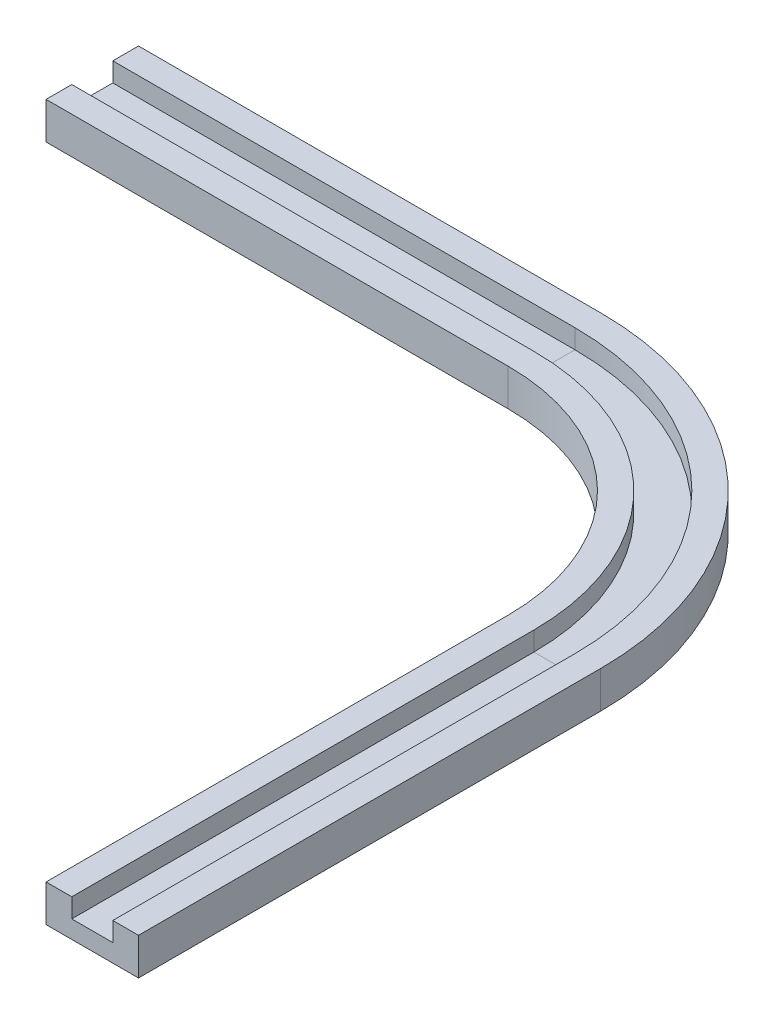
SolidWorks part; units mm, degrees
other "Published References"
other "Ground Plane"
other "Connector1"
other "Connector2"
ref_plane "Front" through (0, 0, 0) normal (0, 0, 1) x (1, 0, 0)
ref_plane "Top" through (0, 0, 0) normal (0, 1, 0) x (1, 0, 0)
ref_plane "Right" through (0, 0, 0) normal (1, 0, 0) x (0, 0, -1)
sketch "Sketch1" plane through (0, 0, 0) normal (0, 1, 0) x (1, 0, 0)
  line L1 (-63.1485, 16.7186) -> (36.8515, 16.7186)
  line L2 (-63.1485, 16.7186) -> (-63.1485, 36.7186)
  line L3 (-63.1485, 36.7186) -> (36.8515, 36.7186)
  line L6 (103.4996, -29.9295) -> (103.4996, -129.9295)
  line L7 (103.4996, -129.9295) -> (83.4996, -129.9295)
  line L8 (83.4996, -29.9295) -> (83.4996, -129.9295)
  arc A0 (36.8515, 36.7186) -> (103.4996, -29.9295) centre (36.8515, -29.9295) cw
  arc A1 (36.8515, 16.7186) -> (83.4996, -29.9295) centre (36.8515, -29.9295) cw
  dimension "D1" = 100
  dimension "D2" = 20
  dimension "D3" = 100
  dimension "D4" = 20
extrude "Boss-Extrude1" add sketch "Sketch1" along normal blind 8 contours L1 A1 L8 L7 L6 A0 L3 L2
sketch "Sketch2" plane through (0, 8, 0) normal (0, 1, 0) x (1, 0, 0)
  line L0 (103.4996, -29.9295) -> (103.4996, -129.9295) construction
  line L1 (-63.1485, 36.7186) -> (36.8515, 36.7186) construction
  line L2 (103.4996, -29.9295) -> (103.4996, -129.9295)
  line L3 (-63.1485, 36.7186) -> (36.8515, 36.7186)
  line L4 (-63.1485, 26.7186) -> (36.8515, 26.7186)
  line L5 (93.4996, -29.9295) -> (93.4996, -129.9295)
  arc A0 (103.4996, -29.9295) -> (36.8515, 36.7186) centre (36.8515, -29.9295) ccw construction
  arc A1 (103.4996, -29.9295) -> (36.8515, 36.7186) centre (36.8515, -29.9295) ccw
  arc A2 (93.4996, -29.9295) -> (36.8515, 26.7186) centre (36.8515, -29.9295) ccw
  dimension "D1" = 10
sketch "Sketch3" plane through (-63.1485, 0, 0) normal (-1, 0, 0) x (0, 0, 1)
  line L0 (29.9295, 8) -> (-36.7186, 8) construction
  line L1 (-31.1581, 8) -> (-22.2791, 8)
  line L2 (-31.1581, 8) -> (-31.1581, 3.8543)
  line L3 (-31.1581, 3.8543) -> (-22.2791, 3.8543)
  line L4 (-22.2791, 8) -> (-22.2791, 3.8543)
  point P6 (-26.7186, 8)
sweep "Cut-Sweep1" cut profiles "Sketch3" path "Sketch2"
